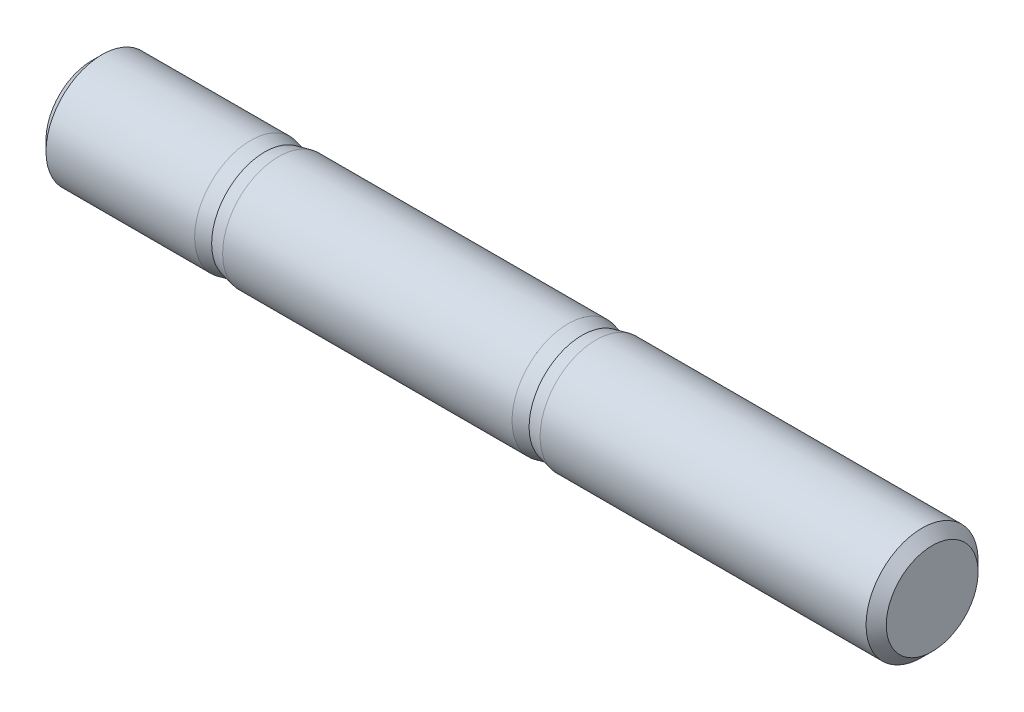
SolidWorks part; units mm, degrees
ref_plane "Front" through (0, 0, 0) normal (0, 0, 1) x (1, 0, 0)
ref_plane "Top" through (0, 0, 0) normal (0, 1, 0) x (1, 0, 0)
ref_plane "Right" through (0, 0, 0) normal (1, 0, 0) x (0, 0, -1)
sketch "Sketch1" plane through (0, 0, 0) normal (0, 0, 1) x (1, 0, 0)
  line L0 (-1.3108, 0) -> (30.3862, 0) construction
  line L1 (0, 0) -> (0, 3)
  line L2 (0, 3) -> (8.5, 3)
  line L3 (8.5, 3) -> (10, 2.675)
  line L4 (10, 2.675) -> (25.5, 2.675)
  line L5 (25.5, 2.675) -> (27, 3)
  line L6 (27, 3) -> (45, 3)
  line L7 (45, 3) -> (45, 0)
  line L8 (45, 0) -> (0, 0)
  dimension "D2" = 1.5
  dimension "l" = 35
  dimension "bm" = 10
  dimension "b" = 18
revolve "BaseHead" add sketch "Sketch1" angle 360 about L0
cosmetic thread "ThreadCosmetic1" [suppressed] parameters "D1"=8.5, "D2"=4.917
cosmetic thread "ThreadCosmetic2" [suppressed] parameters "b"=18, "D2"=4.917
chamfer "HeadChamfer" distance 0.5415 angle 45 2 edges at (0, 0, 3) (45, 0, 3)
sketch "Sketch2" plane through (0, 0, 0) normal (0, 0, 1) x (1, 0, 0)
  line L0 (-1.3108, 0) -> (31.2107, 0) construction
  line L2 (8.5, 2.675) -> (10, 3)
  line L3 (10, 3) -> (25.5, 3)
  line L4 (25.5, 3) -> (27, 2.675)
  line L7 (8.5, 3) -> (8.5, -3) construction
  line L9 (8.5, 2.675) -> (27, 2.675)
  line L10 (27, 3) -> (27, -3) construction
  dimension "D2" = 6
  dimension "D1" = 1.5
revolve "BaseBody" add sketch "Sketch2" angle 360 about L0
sketch "Sketch3" plane through (0, 0, 0) normal (0, 0, 1) x (1, 0, 0)
  line L0 (44.4585, 2.531) -> (44.7293, 3)
  line L1 (44.7293, 3) -> (44.7293, 3.5)
  line L2 (44.7293, 3.5) -> (44.1878, 3.5)
  line L3 (44.1878, 3.5) -> (44.1878, 3)
  line L4 (44.1878, 3) -> (44.4585, 2.531)
  line L5 (0, 0) -> (54.5942, 0) construction
  line L6 (44.4585, 3) -> (44.4585, -3) construction
  dimension "D1" = 60
  dimension "D2" = 60
  dimension "D3" = 0.5
  dimension "D4" = 0.5415
  dimension "D5" = 6
revolve "Cut-Revolve10" [suppressed] cut sketch "Sketch3" angle 360 about L5
pattern_linear "LPattern10" [suppressed] count 28 spacing 0.6498 along (-1, 0, 0) of bodies 103
sketch "Sketch4" plane through (0, 0, 0) normal (0, 0, 1) x (1, 0, 0)
  line L0 (0.5415, 2.531) -> (0.8122, 3)
  line L1 (0.8122, 3) -> (0.8122, 3.5)
  line L2 (0.8122, 3.5) -> (0.2707, 3.5)
  line L3 (0.2707, 3.5) -> (0.2707, 3)
  line L4 (0.2707, 3) -> (0.5415, 2.531)
  line L5 (0, 0) -> (16.1581, 0) construction
  line L6 (0, 2.4585) -> (0, -2.4585) construction
  line L7 (0.5415, 3) -> (0.5415, -3) construction
  dimension "D1" = 60
  dimension "D2" = 60
  dimension "D3" = 0.5
  dimension "D4" = 0.5415
  dimension "D5" = 6
revolve "Cut-Revolve11" [suppressed] cut sketch "Sketch4" angle 360 about L5
pattern_linear "LPattern11" [suppressed] count 13 spacing 0.6498 along (1, 0, 0) of bodies 105
equation "\"D2@Sketch1\" = \"X@Sketch1\""
equation "\"D2@ThreadCosmetic2\" = \"D2@ThreadCosmetic1\""
equation "\"D1@ThreadCosmetic1\" = \"bm@Sketch1\"-\"X@Sketch1\""
equation "\"b@ThreadCosmetic2\" = \"b@Sketch1\""
equation "\"D1@Sketch2\" = \"X@Sketch1\""
equation "\"D2@Sketch2\" = \"d@Sketch1\""
equation "\"D1@HeadChamfer\" =  ( \"d@Sketch1\" - \"D2@ThreadCosmetic1\" )  / 2"
equation "\"D5@Sketch3\" = \"d@Sketch1\""
equation "\"D4@Sketch3\" = (  \"d@Sketch1\" - \"D2@ThreadCosmetic2\" )  / 2"
equation "\"D3@LPattern10\" = \"D4@Sketch3\" * 1.2"
equation "\"D1@LPattern10\" = \"b@ThreadCosmetic2\" / \"D3@LPattern10\""
equation "\"D5@Sketch4\" = \"d@Sketch1\""
equation "\"D4@Sketch4\" = (  \"d@Sketch1\" - \"D2@ThreadCosmetic1\" )  / 2"
equation "\"D3@LPattern11\" = \"D4@Sketch4\" * 1.2"
equation "\"D1@LPattern11\" = \"D1@ThreadCosmetic1\" / \"D3@LPattern11\""
